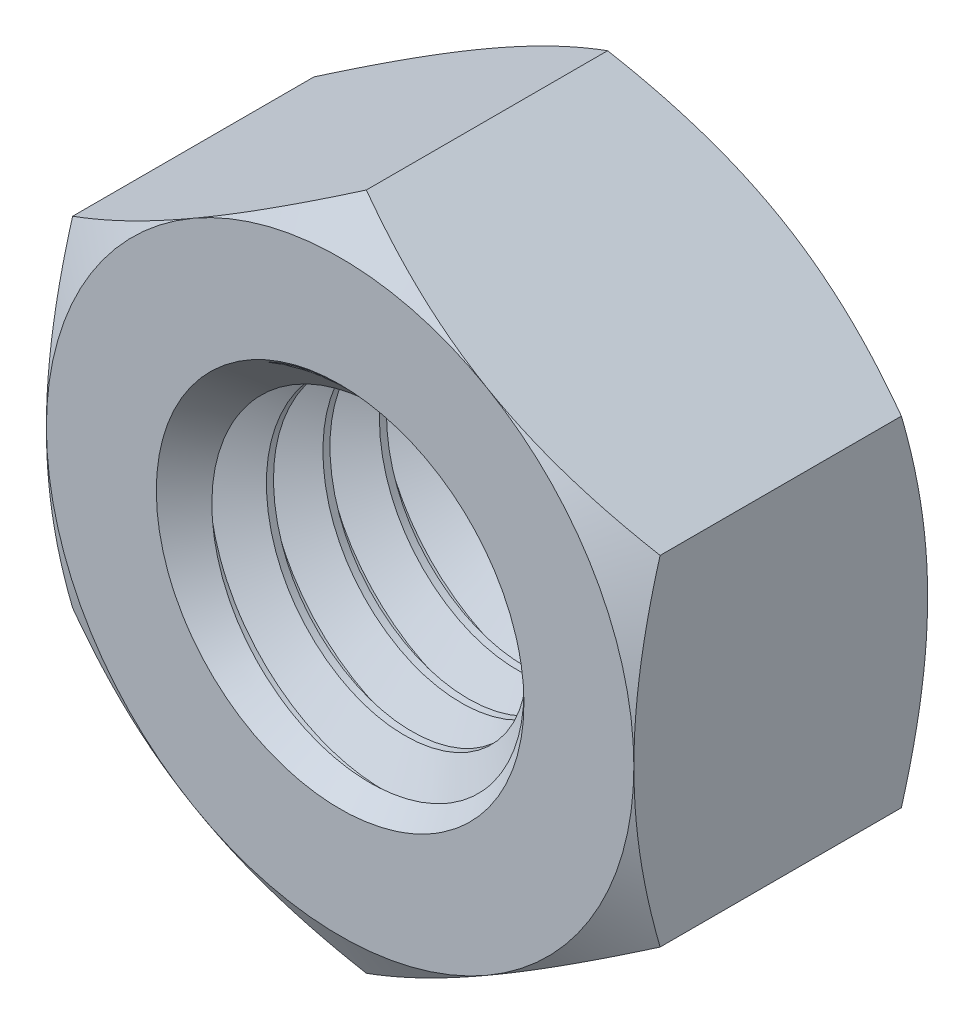
SolidWorks part; units mm, degrees
ref_plane "Front Plane" through (0, 0, 0) normal (0, 0, 1) x (1, 0, 0)
ref_plane "Top Plane" through (0, 0, 0) normal (0, 1, 0) x (1, 0, 0)
ref_plane "Right Plane" through (0, 0, 0) normal (1, 0, 0) x (0, 0, -1)
sketch "Sketch1" plane through (0, 0, 0) normal (1, 0, 0) x (0, 0, -1)
  line L0 (-3.25, 0) -> (3.25, 0) construction
  line L1 (-3.25, -6.5) -> (-3.25, 6.5) construction
  line L2 (3.25, -6.5) -> (3.25, 6.5) construction
  line L3 (-3.25, -4) -> (-3.25, 4) construction
  line L4 (-4.4219, 4.1353) -> (-3.7969, 3.0528) construction
  line L5 (-3.7969, 3.0528) -> (-3.1719, 4.1353) construction
  line L6 (-3.1719, 4.1353) -> (-4.4219, 4.1353) construction
  line L7 (-4.3828, 4.0677) -> (-3.2109, 4.0677) construction
  line L8 (-4.3438, 4) -> (-3.25, 4) construction
  line L9 (-3.875, 3.1881) -> (-3.7188, 3.1881) construction
  line L10 (-3.7969, 3.1881) -> (-3.7969, 3.0528) construction
  line L11 (-3.7969, 4.1353) -> (-3.7969, 4) construction
  point P4 (0, 0)
  point P7 (-3.25, 0)
  point P11 (3.25, 0)
  point P14 (-3.25, 0)
  point P26 (-3.7969, 4.0677)
  point P27 (-3.25, -4)
  dimension "Height" = 6.5
  dimension "Width" = 13
  dimension "Thread OD" = 8
  dimension "D1" = 60
  dimension "Pitch" = 1.25
  dimension "D2" = 0.1563
sketch "Sketch2" plane through (0, 0, 0) normal (0, 0, 1) x (1, 0, 0)
  line L1 (0, 7.5056) -> (-6.5, 3.7528)
  line L2 (-6.5, 3.7528) -> (-6.5, -3.7528)
  line L3 (-6.5, -3.7528) -> (0, -7.5056)
  line L4 (0, -7.5056) -> (6.5, -3.7528)
  line L5 (6.5, -3.7528) -> (6.5, 3.7528)
  line L6 (6.5, 3.7528) -> (0, 7.5056)
  circle A0 centre (0, 0) radius 6.5 construction
  circle A1 centre (0, 0) radius 4
extrude "Boss-Extrude1" add sketch "Sketch2" along normal up to vertex (3.25 mm away) and the other way up to vertex (3.25 mm away) up to point (0, -6.5, 3.25) other way up to point (0, -6.5, -3.25)
sketch "Sketch3" plane through (0, 0, 3.25) normal (0, 0, 1) x (1, 0, 0)
  circle A0 centre (0, 0) radius 6.5
extrude "Cut-Extrude1" cut sketch "Sketch3" against normal through all draft 60 flip side to cut
mirror "Mirror1" about plane through (0, 0, 0) normal (0, 0, 1) of "Cut-Extrude1"
ref_axis "Center Axis 1" through (0, 0, -10.9016) along (0, 0, 1)
ref_plane "Contact Plane 1" through (0, 0, 3.25) normal (0, 0, 1) x (1, 0, 0)
ref_plane "Contact Plane 2" through (0, 0, -3.25) normal (0, 0, -1) x (-1, 0, 0)
sketch "Sketch4" plane through (0, 0, 0) normal (1, 0, 0) x (0, 0, -1)
  line L1 (-4.3828, 4.0677) -> (-3.875, 3.1881)
  line L2 (-3.875, 3.1881) -> (-3.7188, 3.1881)
  line L3 (-3.7188, 3.1881) -> (-3.2109, 4.0677)
  line L4 (-4.3828, 4.0677) -> (-3.2109, 4.0677) construction
  line L5 (-4.3828, 4.0677) -> (-3.2109, 4.0677)
sketch "Sketch5" plane through (0, 0, 3.25) normal (0, 0, 1) x (1, 0, 0)
  circle A0 centre (0, 0) radius 4 construction
  circle A1 centre (0, 0) radius 4
curve "Helix/Spiral1" pitch 1.25 height 7.75 radius 4 centre (0, 0, 3.25) axis (0, 0, -1) start towards (0, 1, 0)
sweep "Sweep1" add profiles "Sketch4" path "Helix/Spiral1"
sketch "Sketch6" plane through (0, 0, 3.25) normal (0, 0, 1) x (1, 0, 0)
  circle A1 centre (0, 0) radius 4.0677
extrude "Cut-Extrude2" cut sketch "Sketch6" along normal through all and the other way through all draft 45
sketch "Sketch7" plane through (0, 0, -3.25) normal (0, 0, -1) x (-1, 0, 0)
  circle A1 centre (0, 0) radius 4.0677
  circle A2 centre (0, 0) radius 4.0677
  dimension "D1" = 0
extrude "Cut-Extrude3" cut sketch "Sketch7" along normal through all and the other way through all draft 45
equation "\"D2@Sketch1\"=\"Pitch@Sketch1\"/8"
equation "\"D4@Helix/Spiral1\"=\"Pitch@Sketch1\""
equation "\"D3@Helix/Spiral1\"=\"Height@Sketch1\"+\"Pitch@Sketch1\""
